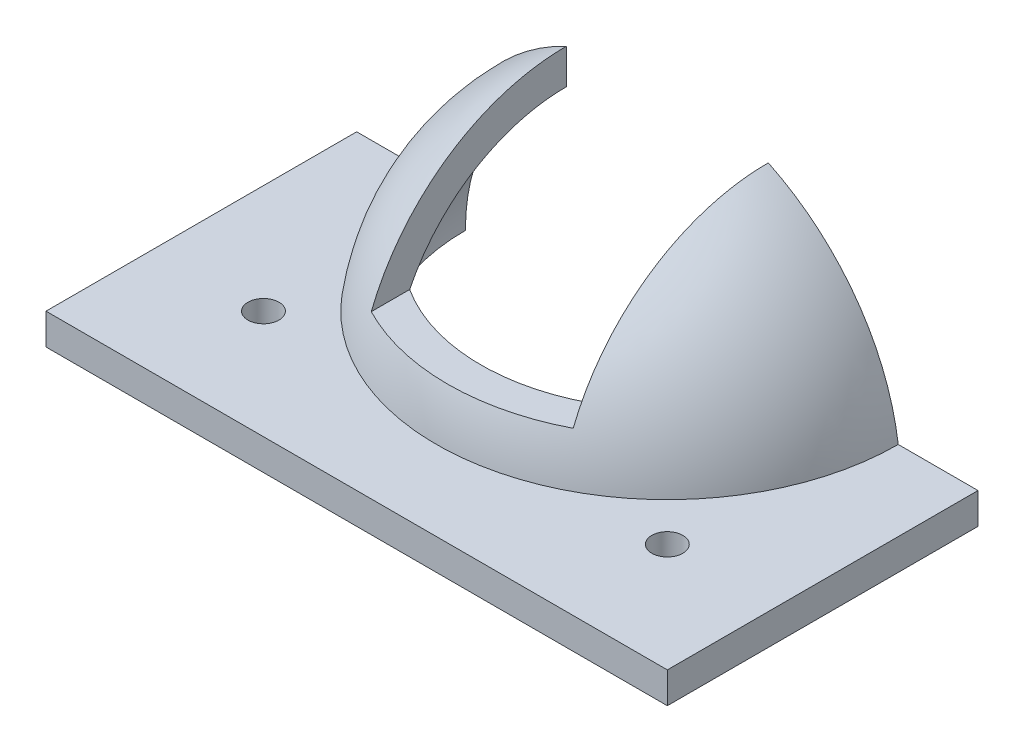
SolidWorks part; units mm, degrees
ref_plane "Front Plane" through (0, 0, 0) normal (0, 0, 1) x (1, 0, 0)
ref_plane "Top Plane" through (0, 0, 0) normal (0, 1, 0) x (1, 0, 0)
ref_plane "Right Plane" through (0, 0, 0) normal (1, 0, 0) x (0, 0, -1)
sketch "Sketch1" plane through (0, 0, 0) normal (0, 0, 1) x (1, 0, 0)
  line L0 (16.51, 0) -> (19.05, 0) construction
  line L1 (19.05, 0) -> (16.51, 0) construction
  line L2 (19.05, 0) -> (16.51, 0)
  line L3 (0, 19.05) -> (0, 16.51)
  arc A0 (19.05, 0) -> (0, 19.05) centre (0, 0) ccw
  arc A2 (16.51, 0) -> (0, 16.51) centre (0, 0) ccw
  circle A3 centre (0, 0) radius 19.05 construction
  circle A4 centre (0, 0) radius 16.51 construction
  dimension "D1" = 38.1
  dimension "D2" = 2.54
revolve "Revolve1" add sketch "Sketch1" angle 360 about L3
sketch "Sketch2" plane through (0, 0, 0) normal (0, 0, 1) x (1, 0, 0)
  line L0 (0, 6.35) -> (0, 0) construction
  line L1 (-8.255, 22.7688) -> (8.255, 22.7688)
  line L2 (-8.255, 22.7688) -> (-8.255, 6.35)
  line L3 (-8.255, 6.35) -> (8.255, 6.35)
  line L4 (8.255, 22.7688) -> (8.255, 6.35)
  dimension "D1" = 6.35
  dimension "D2" = 16.51
extrude "Cut-Extrude1" cut sketch "Sketch2" against normal mid plane 127
sketch "Sketch3" plane through (0, 0, 0) normal (0, -1, 0) x (1, 0, 0)
  line L1 (25.4, -25.4) -> (-25.4, -25.4)
  line L2 (25.4, -25.4) -> (25.4, 25.4)
  line L3 (25.4, 25.4) -> (-25.4, 25.4)
  line L4 (-25.4, -25.4) -> (-25.4, 25.4)
  line L5 (25.4, -25.4) -> (-25.4, 25.4) construction
  line L6 (25.4, 25.4) -> (-25.4, -25.4) construction
  circle A0 centre (0, 0) radius 16.51
  point P0 (0, 0)
  dimension "D2" = 33.02
  dimension "D1" = 50.8
sketch "Sketch4" plane through (0, 0, 0) normal (0, -1, 0) x (1, 0, 0)
  line L0 (25.4, -25.4) -> (-25.4, 25.4) construction
  circle A0 centre (0.1236, -0.1236) radius 16.51
  dimension "D1" = 33.02
extrude "Boss-Extrude1" add sketch "Sketch3" against normal blind 2.54
sketch "Sketch5" plane through (0, 2.54, 0) normal (0, 1, 0) x (1, 0, 0)
  line L0 (-16.51, 25.4) -> (-16.51, 16.51) construction
  line L1 (-25.4, 25.4) -> (25.4, 25.4) construction
  line L2 (-16.51, 16.51) -> (-25.4, 16.51) construction
  line L3 (-25.4, -25.4) -> (-25.4, 25.4) construction
  circle A0 centre (-16.51, 16.51) radius 1.27
  dimension "D2" = 2.54
  dimension "D1" = 8.89
extrude "Cut-Extrude3" cut sketch "Sketch5" against normal through all contours A0
pattern_linear "LPattern1" count 2 spacing 33.02 along (1, 0, 0) count 2 spacing 33.02 along (0, 0, 1) of "Cut-Extrude3"
sketch "Sketch6" plane through (0, 0, 0) normal (0, 0, 1) x (1, 0, 0)
  line L1 (-27.8436, 17.9221) -> (28.4379, 17.9221)
  line L2 (-27.8436, 17.9221) -> (-27.8436, -2.225)
  line L3 (-27.8436, -2.225) -> (28.4379, -2.225)
  line L4 (28.4379, 17.9221) -> (28.4379, -2.225)
extrude "Cut-Extrude4" cut sketch "Sketch6" against normal through all contours L2 L3 L4 L1
